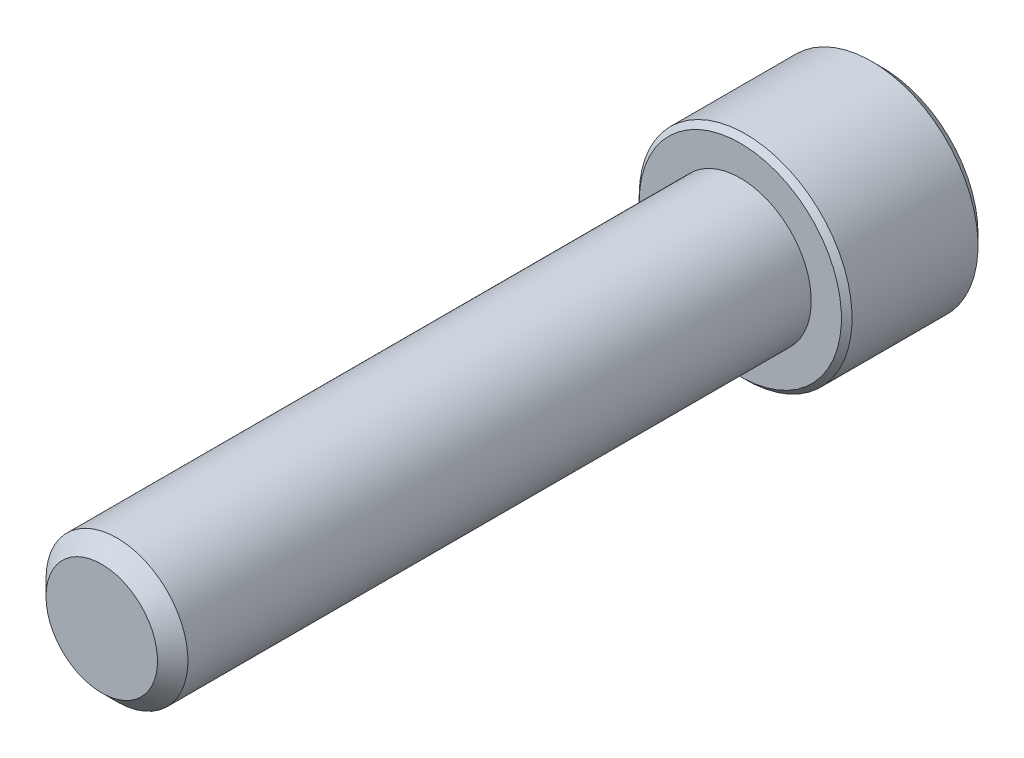
SolidWorks part; units mm, degrees
ref_plane "Front Plane" through (0, 0, 0) normal (0, 0, 1) x (1, 0, 0)
ref_plane "Top Plane" through (0, 0, 0) normal (0, 1, 0) x (1, 0, 0)
ref_plane "Right Plane" through (0, 0, 0) normal (1, 0, 0) x (0, 0, -1)
sketch "Sketch0" plane through (0, 0, 0) normal (1, 0, 0) x (0, 0, -1)
  line L0 (0, 0) -> (28.575, 0) construction
  point P2 (34.925, 0)
  point P4 (0, 0)
  dimension "D1" = 28.575
  dimension "D2" = 6.35
  dimension "Min Thread" = 0
sketch "Sketch1" plane through (0, 0, 0) normal (0, 0, 1) x (1, 0, 0)
  circle A0 centre (0, 0) radius 3.175
  dimension "OD" = 6.35
extrude "Extrude1" add sketch "Sketch1" against normal blind 28.575
sketch "Sketch2" plane through (0, 0, 0) normal (0, 0, 1) x (1, 0, 0)
  circle A0 centre (0, 0) radius 3.175 construction
  circle A1 centre (0, 0) radius 3.175
curve "Helix/Spiral1" pitch 0.9071 height 29.4821 turns 32.5 parameters "pitch"=0.9071
chamfer "Chamfer3" distance 0.6804 angle 45 1 edges at (3.175, 0, 0)
sketch "Sketch3" plane through (0, 0, 0) normal (1, 0, 0) x (0, 0, -1)
  line L0 (-0.7937, 3.175) -> (-0.4536, 2.5858)
  line L1 (-0.4536, 2.5858) -> (-0.3402, 2.5858)
  line L2 (-0.3402, 2.5858) -> (0, 3.175)
  line L3 (-0.7937, 3.175) -> (0, 3.175)
  line L4 (-0.3969, 3.175) -> (-0.3969, 2.5858) construction
  line L5 (-0.6237, 2.8804) -> (-0.1701, 2.8804) construction
  line L6 (0, 3.175) -> (0, -3.175) construction
  dimension "D1" = 0.1134
  dimension "D2" = 0.4536
  dimension "D3" = 60
sweep "Cut-Sweep1" [suppressed] cut profiles "Sketch3" path "Helix/Spiral1"
sketch "Sketch5" [suppressed] plane through (0, 0, 0) normal (1, 0, 0) x (0, 0, -1)
  line L0 (28.575, -2.2654) -> (28.575, 2.5962) construction
  line L1 (28.575, 3.175) -> (0, 3.175)
  line L2 (28.575, 3.175) -> (28.575, 0)
  line L3 (28.575, 0) -> (-1.1556, 0)
  line L4 (0, 0) -> (28.575, 0) construction
  line L5 (0, 3.175) -> (-1.1556, 0)
  line L6 (0, 0) -> (31.115, 0) construction
  dimension "D1" = 70
  dimension "D3" = 2.54
revolve "partially thread" [suppressed] add sketch "Sketch5" angle 360 about L6
sketch "Sketch6" plane through (0, 0, -28.575) normal (0, 0, -1) x (-1, 0, 0)
  circle A0 centre (0, 0) radius 4.7625
  dimension "head dia" = 9.525
extrude "Extrude2" add sketch "Sketch6" along normal blind 6.35
sketch "Sketch7" plane through (0, 0, -34.925) normal (0, 0, -1) x (-1, 0, 0)
  line L1 (0, 2.7496) -> (-2.3813, 1.3748)
  line L2 (-2.3813, 1.3748) -> (-2.3813, -1.3748)
  line L3 (-2.3813, -1.3748) -> (0, -2.7496)
  line L4 (0, -2.7496) -> (2.3813, -1.3748)
  line L5 (2.3813, -1.3748) -> (2.3813, 1.3748)
  line L6 (2.3813, 1.3748) -> (0, 2.7496)
  circle A0 centre (0, 0) radius 2.3813 construction
  dimension "hex dia" = 4.7625
extrude "Cut-Extrude1" cut sketch "Sketch7" against normal blind 3.5719
sketch "Sketch8" plane through (0, 0, -34.925) normal (0, 0, -1) x (-1, 0, 0)
  circle A0 centre (0, 0) radius 2.7496
extrude "Cut-Extrude2" cut sketch "Sketch8" against normal through all draft 45
chamfer "Chamfer1" distance 0.4763 angle 45 1 edges at (-4.7625, 0, -34.925)
chamfer "Chamfer2" distance 0.2381 angle 45 1 edges at (-4.7625, 0, -28.575)
sketch "Sketch9" plane through (0, 0, 0) normal (1, 0, 0) x (0, 0, -1)
  line L0 (0, 3.175) -> (0, -3.175) construction
  line L1 (2.2679, 3.175) -> (2.2679, -3.175) construction
  line L2 (34.925, 4.7625) -> (34.925, -4.7625) construction
  line L3 (28.575, 4.7625) -> (28.575, -4.7625) construction
  line L4 (28.575, 4.5244) -> (28.575, -4.5244) construction
  line L5 (34.925, -4.2863) -> (34.925, 4.2863) construction
  line L6 (28.575, -4.7625) -> (28.575, 4.7625) construction
  line L7 (0, 2.4946) -> (0, -2.4946) construction
  line L8 (-0.7937, 3.175) -> (0, 3.175) construction
  line L9 (2.2679, 0) -> (0, 0) construction
  dimension "D1" = 2.2679
equation "\"D3@Helix/Spiral1\" = \"screw length@Extrude1\"+\"pitch@Helix/Spiral1\""
equation "\"D1@Sketch3\" = \"pitch@Helix/Spiral1\"*.125"
equation "\"D2@Sketch3\" = \"pitch@Helix/Spiral1\"*.5"
equation "\"D1@Cut-Extrude1\" = \"hex dia@Sketch7\"*.75"
equation "\"D1@Chamfer1\" = \"head dia@Sketch6\"*.05"
equation "\"D1@Sketch9\" = \"pitch@Helix/Spiral1\"*2.50"
equation "\"D1@Chamfer2\" = \"D1@Chamfer1\"/2"
equation "\"D1@Chamfer3\" = \"pitch@Helix/Spiral1\"*.750"
equation "\"D1@Sketch0\" = \"screw length@Extrude1\""
equation "\"D2@Sketch0\" = \"head depth@Extrude2\""
